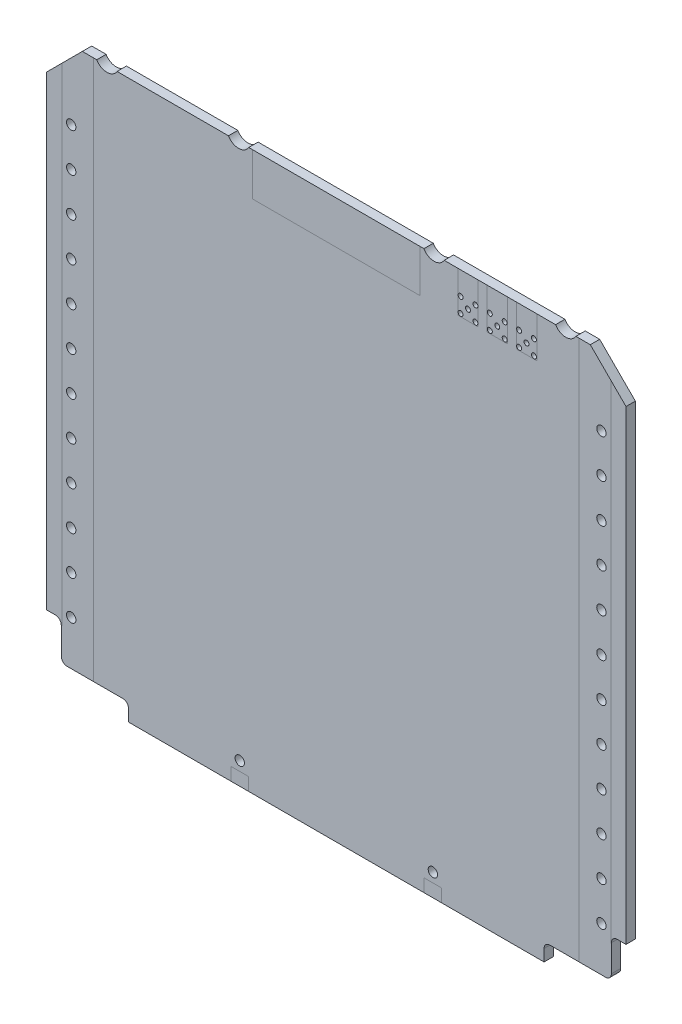
SolidWorks part; units mm, degrees
material "FR4_stuffedProtoboard"
ref_plane "Front Plane" through (0, 0, 0) normal (0, 0, 1) x (1, 0, 0)
ref_plane "Top Plane" through (0, 0, 0) normal (0, 1, 0) x (1, 0, 0)
ref_plane "Right Plane" through (0, 0, 0) normal (1, 0, 0) x (0, 0, -1)
ref_plane "Plane4" through (0, 0, -0.0125) normal (0, 0, -1) x (-1, 0, 0)
sketch "Sketch1" plane through (0, 0, -0.0125) normal (0, 0, -1) x (-1, 0, 0)
  line L4 (49.5, -50) -> (49.5, 45.3)
  line L6 (49.5, 45.3) -> (-49.5, 45.3)
  line L12 (-49.5, 45.3) -> (-49.5, -50)
  line L17 (-49.5, -50) -> (49.5, -50)
  line L18 (0, -50) -> (0, 45.3) construction
  dimension "D7" = 95.3
  dimension "D1" = 99
  dimension "D34" = 50
extrude "basicSize" add sketch "Sketch1" against normal blind 1.6
chamfer "Chamfer1" distance 6.1 angle 45 2 edges at (49.5, 45.3, 0.7875) (-49.5, 45.3, 0.7875)
sketch "Sketch4" plane through (0, 0, 1.5875) normal (0, 0, 1) x (1, 0, 0)
  line L1 (37.4679, 45.3) -> (40.9321, 45.3)
  line L7 (-43.4, 45.3) -> (43.4, 45.3) construction
  line L8 (49.5, 39.2) -> (49.5, -50) construction
  arc A0 (40.9321, 45.3) -> (37.4679, 45.3) centre (39.2, 46.3) cw
  point P5 (39.2, 44.3)
  dimension "D1" = 2
  dimension "D3" = 10.3
  dimension "D2" = 1
extrude "backplaneSideScrewCutout" cut sketch "Sketch4" against normal through all both and the other way through all
pattern_linear "LPattern3" count 2 spacing 22.5 along (-1, 0, 0) of "backplaneSideScrewCutout"
mirror "Mirror3" about plane through (0, 0, 0) normal (1, 0, 0) of "LPattern3"
sketch "Sketch6" plane through (0, 0, 1.5875) normal (0, 0, 1) x (1, 0, 0)
  line L0 (-49.5, -50) -> (-49.5, 39.2) construction
  line L1 (-49.5, -40.4) -> (-47, -40.4)
  line L2 (-49.5, -40.4) -> (-49.5, -50)
  line L4 (-47, -40.4) -> (-47, -47)
  line L5 (49.5, -50) -> (-49.5, -50) construction
  line L6 (-35.5, -50) -> (-49.5, -50)
  line L7 (-35.5, -50) -> (-35.5, -47)
  line L8 (-35.5, -47) -> (-47, -47)
  dimension "D1" = 2.5
  dimension "D2" = 3
  dimension "D3" = 9.6
  dimension "D4" = 14
extrude "Cut-Extrude4" cut sketch "Sketch6" against normal through all
fillet "Fillet1" radius 1 3 edges at (-35.5, -47, 0.7875) (-47, -47, 0.7875) (-47, -40.4, 0.7875)
mirror "Mirror1" about plane through (0, 0, 0) normal (1, 0, 0) of "Cut-Extrude4", "Fillet1"
sketch "Sketch5" plane through (0, 0, 1.5875) normal (0, 0, 1) x (1, 0, 0)
  line L0 (21.23, 41.37) -> (23.77, 38.83) construction
  line L1 (21.23, 38.83) -> (21.23, 41.37) construction
  line L2 (21.23, 41.37) -> (23.77, 41.37) construction
  line L4 (49.5, 39.2) -> (49.5, -40.4) construction
  line L5 (-14.9679, 45.3) -> (14.9679, 45.3) construction
  circle A0 centre (22.5, 40.1) radius 0.425
  circle A1 centre (21.23, 41.37) radius 0.425
  circle A3 centre (21.23, 38.83) radius 0.425
  circle A4 centre (23.77, 41.37) radius 0.425
  circle A5 centre (23.77, 38.83) radius 0.425
  dimension "D2" = 0.85
  dimension "D1" = 2.54
  dimension "D3" = 3.93
  dimension "D4" = 28.27
extrude "Cut-Extrude3" cut sketch "Sketch5" against normal through all
pattern_linear "LPattern2" count 3 spacing 5 along (1, 0, 0) of "Cut-Extrude3"
sketch "partFootprints" plane through (0, 0, 1.5875) normal (0, 0, 1) x (1, 0, 0)
  line L1 (18.4321, 45.3) -> (37.4679, 45.3) construction
  line L6 (20.75, 45.3) -> (20.75, 38.35)
  line L7 (20.75, 38.35) -> (24.25, 38.35)
  line L8 (24.25, 38.35) -> (24.25, 45.3)
  line L9 (24.25, 45.3) -> (20.75, 45.3)
  line L10 (25.75, 45.3) -> (25.75, 38.35)
  line L11 (25.75, 38.35) -> (29.25, 38.35)
  line L12 (29.25, 38.35) -> (29.25, 45.3)
  line L13 (29.25, 45.3) -> (25.75, 45.3)
  line L14 (30.75, 45.3) -> (30.75, 38.35)
  line L15 (30.75, 38.35) -> (34.25, 38.35)
  line L16 (34.25, 38.35) -> (34.25, 45.3)
  line L17 (34.25, 45.3) -> (30.75, 45.3)
  line L19 (32.5, 38.35) -> (32.5, 40.1) construction
  line L23 (22.5, 38.35) -> (22.5, 40.1) construction
  circle A2 centre (22.5, 40.1) radius 0.425 construction
  circle A5 centre (32.5, 40.1) radius 0.425 construction
  dimension "D1" = 1.75
  dimension "D8" = 3.5
  dimension "D6" = 3
extrude "MMCXfootprint" cut sketch "partFootprints" against normal blind 0.0001
sketch "Sketch7" plane through (0, 0, 1.5875) normal (0, 0, 1) x (1, 0, 0)
  line L0 (-14.2875, 45.5) -> (-14.2875, 39.912) construction
  line L1 (-14.2875, 45.3) -> (-14.2875, 38.007)
  line L2 (-12.2428, 38.007) -> (-11.8872, 38.007) construction
  line L3 (-14.2875, 38.007) -> (14.2875, 38.007)
  line L4 (14.2875, 45.5) -> (14.2875, 39.912) construction
  line L5 (14.2875, 45.3) -> (14.2875, 38.007)
  line L7 (-14.9679, 45.3) -> (14.9679, 45.3) construction
  line L8 (-14.2875, 45.3) -> (14.2875, 45.3)
extrude "TigerEyeFootprint" cut sketch "Sketch7" against normal blind 0.0001
sketch "thermalContacts_upper" plane through (0, 0, 1.5875) normal (0, 0, 1) x (1, 0, 0)
  line L0 (-49.5, -40.4) -> (-49.5, 39.2) construction
  line L1 (35.5, -50) -> (-35.5, -50) construction
  line L3 (-46.9, 45.3) -> (-46.9, -41.5)
  line L4 (-37.4679, 45.3) -> (-18.4321, 45.3) construction
  line L23 (-46.9, 45.3) -> (-56.3922, 45.3)
  line L24 (-56.3922, 45.3) -> (-56.3922, -41.5)
  line L25 (-56.3922, -41.5) -> (-46.9, -41.5)
  dimension "D1" = 2.6
  dimension "D2" = 8.5
extrude "keepOut_bottom" cut sketch "thermalContacts_upper" against normal blind 0.0001
sketch "Sketch3" plane through (0, 0, 1.5875) normal (0, 0, 1) x (1, 0, 0)
  line L0 (18.4321, 45.3) -> (20.75, 45.3) construction
  line L1 (-47, -46) -> (-47, -41.5) construction
  line L2 (-36.5, -47) -> (-46, -47) construction
  line L5 (-49.5, -40.4) -> (-49.5, 39.2) construction
  line L6 (-46.9, -41.5) -> (-46.9, 41.8) construction
  line L7 (-46.9, -41.5) -> (-47, -41.5)
  line L8 (-47, -46) -> (-47, -41.5) construction
  line L9 (-47, -41.5) -> (-46.9, -41.5) construction
  line L10 (0, -50) -> (0, 45.3) construction
  line L11 (35.5, -50) -> (-35.5, -50) construction
  line L12 (-43.4, 45.3) -> (-40.9321, 45.3) construction
  line L13 (-41.5, 45.3) -> (-46.9, 45.3)
  line L14 (-46, -47) -> (-41.5, -47)
  line L15 (-47, -41.5) -> (-47, -46)
  line L16 (-46.9, 45.3) -> (-46.9, -41.5)
  line L17 (-41.5, -47) -> (-41.5, 45.3)
  arc A3 (-47, -46) -> (-46, -47) centre (-46, -46) ccw construction
  arc A4 (-46, -47) -> (-47, -46) centre (-46, -46) cw
  dimension "D1" = 8
extrude "caution_top" cut sketch "Sketch3" against normal blind 0.0001
sketch "hold-downLocations" plane through (0, 0, 1.5875) normal (0, 0, 1) x (1, 0, 0)
  line L1 (-18, -47.8) -> (-15, -47.8) construction
  line L3 (15, -47.8) -> (18, -47.8)
  line L4 (18, -47.8) -> (18, -50)
  line L5 (35.5, -50) -> (-35.5, -50) construction
  line L6 (18, -50) -> (15, -50)
  line L7 (15, -50) -> (15, -47.8)
  line L8 (-15, -47.8) -> (-15, -50) construction
  line L9 (-15, -50) -> (-18, -50) construction
  line L10 (-18, -50) -> (-18, -47.8) construction
  line L11 (0, -50) -> (0, -47.8) construction
  line L12 (-15, -47.8) -> (15, -47.8) construction
  dimension "D1" = 3
  dimension "D2" = 2.2
  dimension "D3" = 3
  dimension "D5" = 30
extrude "hold-downFootprints" cut sketch "hold-downLocations" against normal blind 0.0001
ref_plane "midplane_Z" through (0, 0, 0.7875) normal (0, 0, 1) x (1, 0, 0)
mirror "clearances_top-bottom" about plane through (0, 0, 0.7875) normal (0, 0, 1) of "hold-downFootprints", "caution_top", "keepOut_bottom"
mirror "clearances_side-side" about plane through (0, 0, 0) normal (1, 0, 0) of "clearances_top-bottom"
sketch "Sketch10" plane through (0, 0, -0.0125) normal (0, 0, -1) x (-1, 0, 0)
  line L0 (-15, -47.8) -> (-15, -50) construction
  line L1 (-18, -47.8) -> (-15, -47.8)
  line L2 (-18, -47.8) -> (-18, -44.5)
  line L3 (-18, -44.5) -> (-15, -44.5)
  line L4 (-15, -47.8) -> (-15, -44.5)
  line L5 (-15, -50) -> (15, -50) construction
  line L6 (0, -50) -> (0, -41.5199) construction
  line L7 (15, -47.8) -> (15, -44.5)
  line L8 (18, -44.5) -> (15, -44.5)
  line L9 (18, -47.8) -> (18, -44.5)
  line L10 (18, -47.8) -> (15, -47.8)
  dimension "D1" = 5.5
extrude "bottomsideShelfKeepouts" cut sketch "Sketch10" against normal up to surface (0.0001 mm away) up to face at (16.5, -48.9, -0.0124)
sketch "recommendedBuildArea" [suppressed] plane through (0, 0, 1.5875) normal (0, 0, 1) x (1, 0, 0)
  line L0 (51.1146, 38.007) -> (51.1146, 56.8216) construction
  line L1 (-35.5, -45.5) -> (-46.8, -45.5) construction
  line L2 (-35.5, -47) -> (-35.5, -45.5) construction
  line L3 (35.5, -47) -> (35.5, -45.5) construction
  line L4 (14.2875, 45.3) -> (-14.2875, 45.3)
  line L5 (-14.2875, 45.3) -> (-14.2875, 38.007)
  line L6 (-14.2875, 38.007) -> (14.2875, 38.007)
  line L7 (-46.8, 41.9) -> (-49.5, 39.2)
  line L8 (-49.5, 39.2) -> (-49.5, -40.4)
  line L9 (-49.5, -40.4) -> (-48, -40.4)
  line L10 (-46.8, -41.5) -> (-46.8, 41.9)
  line L11 (-47, -41.4) -> (-47, -41.5)
  line L12 (-47, -41.4) -> (-47, -41.5)
  line L13 (-47, -41.5) -> (-46.8, -41.5)
  line L14 (35.5, -45.5) -> (46.8, -45.5) construction
  line L15 (54.1146, 35.007) -> (54.1146, 77.997)
  line L16 (54.1146, 77.997) -> (43.8, 42.325)
  line L17 (-46.8, -45.5) -> (-46.8, 41.9) construction
  line L20 (43.8, 42.325) -> (43.8, -42.5)
  line L21 (14.2875, 38.007) -> (14.2875, 45.3)
  line L22 (32.5, -42.5) -> (43.8, -42.5)
  line L23 (-14.2875, 45.3) -> (-14.2875, 38.007)
  line L24 (-14.2875, 38.007) -> (51.1146, 38.007)
  line L25 (32.5, -47) -> (32.5, -42.5)
  line L26 (32.5, -47) -> (32.5, -47)
  line L27 (21, -47) -> (32.5, -47)
  line L28 (21, -45) -> (21, -47)
  line L29 (46.8, -41.5) -> (47, -41.5)
  line L30 (46.8, -41.5) -> (47, -41.5)
  line L31 (46.8, 41.9) -> (46.8, -41.5)
  line L32 (48, -40.4) -> (49.5, -40.4)
  line L33 (49.5, -40.4) -> (49.5, 39.2)
  line L34 (49.5, 39.2) -> (46.8, 41.9)
  line L35 (47, -41.5) -> (47, -41.4)
  line L36 (12, -45) -> (21, -45)
  line L37 (47, -41.5) -> (47, -41.4)
  line L38 (46.8, 41.9) -> (46.8, -45.5) construction
  line L39 (12, -47) -> (12, -45)
  line L40 (-12, -47) -> (12, -47)
  line L41 (-12, -45) -> (-12, -47)
  line L42 (-21, -45) -> (-12, -45)
  line L43 (-21, -47) -> (-21, -45)
  line L44 (-32.5, -47) -> (-21, -47)
  line L45 (-32.5, -47) -> (-32.5, -47)
  line L46 (-32.5, -47) -> (-32.5, -42.5)
  line L47 (-32.5, -42.5) -> (-43.8, -42.5)
  line L48 (-43.8, -42.5) -> (-43.8, 34.7661)
  line L49 (-43.8, 34.7661) -> (-43.8, 34.7661)
  line L50 (-43.8, 34.7661) -> (-39.8793, 42.3)
  line L51 (-17.2875, 42.3) -> (-39.8793, 42.3)
  line L52 (-17.2875, 42.3) -> (-17.2875, 35.007)
  line L53 (-17.2875, 35.007) -> (54.1146, 35.007)
  line L59 (-47, -41.5) -> (-46.8, -41.5)
  line L72 (-15, -48) -> (-15, -50)
  line L73 (-15, -50) -> (15, -50)
  line L74 (15, -50) -> (15, -48)
  line L75 (15, -48) -> (18, -48)
  line L76 (18, -48) -> (18, -50)
  line L77 (18, -50) -> (35.5, -50)
  line L78 (35.5, -50) -> (35.5, -48)
  line L79 (36.5, -47) -> (41.5, -47)
  line L80 (41.5, -47) -> (41.5, 45.3)
  line L81 (41.5, 45.3) -> (40.9321, 45.3)
  line L82 (37.4679, 45.3) -> (34.25, 45.3)
  line L83 (34.25, 45.3) -> (34.25, 38.35)
  line L84 (34.25, 38.35) -> (30.75, 38.35)
  line L85 (30.75, 38.35) -> (30.75, 45.3)
  line L86 (30.75, 45.3) -> (29.25, 45.3)
  line L87 (29.25, 45.3) -> (29.25, 38.35)
  line L88 (29.25, 38.35) -> (25.75, 38.35)
  line L89 (25.75, 38.35) -> (25.75, 45.3)
  line L90 (25.75, 45.3) -> (24.25, 45.3)
  line L91 (24.25, 45.3) -> (24.25, 38.35)
  line L92 (24.25, 38.35) -> (20.75, 38.35)
  line L93 (20.75, 38.35) -> (20.75, 45.3)
  line L94 (20.75, 45.3) -> (18.4321, 45.3)
  line L95 (14.9679, 45.3) -> (14.2875, 45.3)
  line L96 (14.2875, 45.3) -> (14.2875, 38.007)
  line L97 (14.2875, 38.007) -> (-14.2875, 38.007)
  line L98 (-14.2875, 38.007) -> (-14.2875, 45.3)
  line L99 (-14.2875, 45.3) -> (-14.9679, 45.3)
  line L100 (-18.4321, 45.3) -> (-37.4679, 45.3)
  line L101 (-40.9321, 45.3) -> (-41.5, 45.3)
  line L102 (41.5, -47) -> (41.5, 45.3)
  line L103 (-41.5, -47) -> (-36.5, -47)
  line L104 (-35.5, -48) -> (-35.5, -50)
  line L105 (-35.5, -50) -> (-18, -50)
  line L106 (-18, -50) -> (-18, -48)
  line L107 (-18, -48) -> (-15, -48)
  line L108 (-15, -48) -> (-15, -50) construction
  line L109 (-15, -50) -> (15, -50) construction
  line L110 (15, -50) -> (15, -48) construction
  line L111 (15, -48) -> (18, -48) construction
  line L112 (18, -48) -> (18, -50) construction
  line L113 (18, -50) -> (35.5, -50) construction
  line L114 (35.5, -50) -> (35.5, -47) construction
  line L115 (35.5, -47) -> (41.5, -47) construction
  line L133 (51.1146, 38.007) -> (-14.2875, 38.007)
  line L134 (-14.2875, 38.007) -> (-14.2875, 45.3)
  line L136 (-14.2875, 45.3) -> (-41.7, 45.3) construction
  line L139 (-41.5, -47) -> (-35.5, -47) construction
  line L140 (-35.5, -47) -> (-35.5, -50) construction
  line L141 (-35.5, -50) -> (-18, -50) construction
  line L142 (-18, -50) -> (-18, -48) construction
  line L143 (-18, -48) -> (-15, -48) construction
  line L144 (-46.8, 35.5) -> (-41.7, 45.3) construction
  line L160 (-41.5, 45.3) -> (-41.5, -47)
  line L161 (-41.5, 45.3) -> (-41.5, -47)
  line L162 (-46.8, 41.9) -> (-46.8, 35.5) construction
  line L163 (51.1146, 56.8216) -> (46.8, 41.9) construction
  arc A1 (-47, -41.4) -> (-48, -40.4) centre (-48, -41.4) ccw
  arc A3 (48, -40.4) -> (47, -41.4) centre (48, -41.4) ccw
  arc A10 (36.5, -47) -> (35.5, -48) centre (36.5, -48) ccw
  arc A11 (37.4679, 45.3) -> (40.9321, 45.3) centre (39.2, 46.3) ccw
  arc A12 (14.9679, 45.3) -> (18.4321, 45.3) centre (16.7, 46.3) ccw
  arc A13 (-18.4321, 45.3) -> (-14.9679, 45.3) centre (-16.7, 46.3) ccw
  arc A14 (-40.9321, 45.3) -> (-37.4679, 45.3) centre (-39.2, 46.3) ccw
  arc A15 (-35.5, -48) -> (-36.5, -47) centre (-36.5, -48) ccw
  dimension "D5" = 1.5
  dimension "D1" = 0
  dimension "D2" = 0
  dimension "D3" = 0
  dimension "D4" = 0
  dimension "D6" = 3
ref_point "rail midpoint"
sketch "locatorSketch" plane through (0, 0, 1.5875) normal (0, 0, 1) x (1, 0, 0)
  line L0 (-12.2428, 39.531) -> (12.2428, 38.007) construction
  line L1 (12.2428, 39.531) -> (-12.2428, 38.007) construction
  line L4 (-12.2428, 38.261) -> (-12.2428, 38.007)
  line L5 (-11.8872, 38.261) -> (-12.2428, 38.261)
  line L6 (-11.8872, 38.007) -> (-11.8872, 38.261)
  line L7 (-12.2428, 38.007) -> (-11.8872, 38.007)
  line L8 (-12.2428, 38.261) -> (-12.2428, 38.007)
  line L9 (-11.8872, 38.261) -> (-12.2428, 38.261)
  line L10 (-11.8872, 38.007) -> (-11.8872, 38.261)
  line L11 (-12.2428, 38.007) -> (-11.8872, 38.007)
  line L12 (-12.2428, 39.531) -> (-12.2428, 39.277)
  line L13 (-11.8872, 39.531) -> (-12.2428, 39.531)
  line L14 (-11.8872, 39.277) -> (-11.8872, 39.531)
  line L15 (-12.2428, 39.277) -> (-11.8872, 39.277)
  line L16 (-12.2428, 39.531) -> (-12.2428, 39.277)
  line L17 (-11.8872, 39.531) -> (-12.2428, 39.531)
  line L18 (-11.8872, 39.277) -> (-11.8872, 39.531)
  line L19 (-12.2428, 39.277) -> (-11.8872, 39.277)
  line L20 (11.8872, 39.531) -> (11.8872, 39.277)
  line L21 (12.2428, 39.531) -> (11.8872, 39.531)
  line L22 (12.2428, 39.277) -> (12.2428, 39.531)
  line L23 (11.8872, 39.277) -> (12.2428, 39.277)
  line L24 (11.8872, 39.531) -> (11.8872, 39.277)
  line L25 (12.2428, 39.531) -> (11.8872, 39.531)
  line L26 (12.2428, 39.277) -> (12.2428, 39.531)
  line L27 (11.8872, 39.277) -> (12.2428, 39.277)
  line L28 (11.8872, 38.261) -> (11.8872, 38.007)
  line L29 (12.2428, 38.261) -> (11.8872, 38.261)
  line L30 (12.2428, 38.007) -> (12.2428, 38.261)
  line L31 (11.8872, 38.007) -> (12.2428, 38.007)
  line L32 (11.8872, 38.261) -> (11.8872, 38.007)
  line L33 (12.2428, 38.261) -> (11.8872, 38.261)
  line L34 (12.2428, 38.007) -> (12.2428, 38.261)
  line L35 (11.8872, 38.007) -> (12.2428, 38.007)
  dimension "D1" = 0
  dimension "D2" = 0
  dimension "D3" = 0
  dimension "D4" = 0
sketch "Sketch8" plane through (0, 0, 1.5875) normal (0, 0, 1) x (1, 0, 0)
  line L0 (-49.5, -40.4) -> (-48, -40.4) construction
  line L2 (-49.5, -40.4) -> (-49.5, 39.2) construction
  line L3 (-41.5, 45.3) -> (-43.4, 45.3) construction
  line L4 (-18, -47.8) -> (-15, -47.8) construction
  line L5 (-45.3, 33.5) -> (-46.9, 33.5) construction
  line L6 (-46.9, 41.8) -> (-46.9, -41.5) construction
  line L7 (-16.5, -46.2) -> (-16.5, -47.8) construction
  line L8 (-18, -47.8) -> (-15, -47.8) construction
  circle A0 centre (-45.3, 33.5) radius 0.8
  circle A1 centre (-45.3, 26.8727) radius 0.8
  circle A2 centre (-45.3, 20.2455) radius 0.8
  circle A3 centre (-45.3, 13.6182) radius 0.8
  circle A4 centre (-45.3, 6.9909) radius 0.8
  circle A5 centre (-45.3, 0.3636) radius 0.8
  circle A6 centre (-45.3, -6.2636) radius 0.8
  circle A7 centre (-45.3, -12.8909) radius 0.8
  circle A8 centre (-45.3, -19.5182) radius 0.8
  circle A9 centre (-45.3, -26.1455) radius 0.8
  circle A10 centre (-45.3, -32.7727) radius 0.8
  circle A11 centre (-45.3, -39.4) radius 0.8
  circle A12 centre (-16.5, -46.2) radius 0.8
  point P35 (-16.5, -47.8)
  dimension "D1" = 1.6
  dimension "D3" = 1
  dimension "D5" = 4.2
  dimension "D6" = 11.8
  dimension "D2" = 12
extrude "springPinHoleSeed" cut sketch "Sketch8" against normal blind 10
mirror "Mirror4" about plane through (0, 0, 0) normal (1, 0, 0) of "springPinHoleSeed"
sketch "Sketch9" plane through (0, 0, 1.5875) normal (0, 0, 1) x (1, 0, 0)
  circle A0 centre (-45.3, 33.5) radius 1.35
  dimension "D1" = 2.7
sketch "bottomsideKeepout_trace" plane through (0, 0, -0.0125) normal (0, 0, -1) x (-1, 0, 0)
  line L0 (18, -50) -> (18, -44.5) construction
  line L1 (18, -44.5) -> (15, -44.5) construction
  line L2 (15, -44.5) -> (15, -50) construction
  line L3 (-15, -44.5) -> (-15, -50) construction
  line L4 (-15, -44.5) -> (-18, -44.5) construction
  line L5 (-18, -50) -> (-18, -44.5) construction
  line L6 (18, -50) -> (18, -44.5)
  line L7 (18, -44.5) -> (15, -44.5)
  line L8 (15, -44.5) -> (15, -50)
  line L9 (-15, -44.5) -> (-15, -50)
  line L10 (-15, -44.5) -> (-18, -44.5)
  line L11 (-18, -50) -> (-18, -44.5)
  line L12 (15, -50) -> (18, -50) construction
  line L13 (-15, -50) -> (-18, -50) construction
  line L14 (15, -50) -> (18, -50)
  line L15 (-15, -50) -> (-18, -50)
